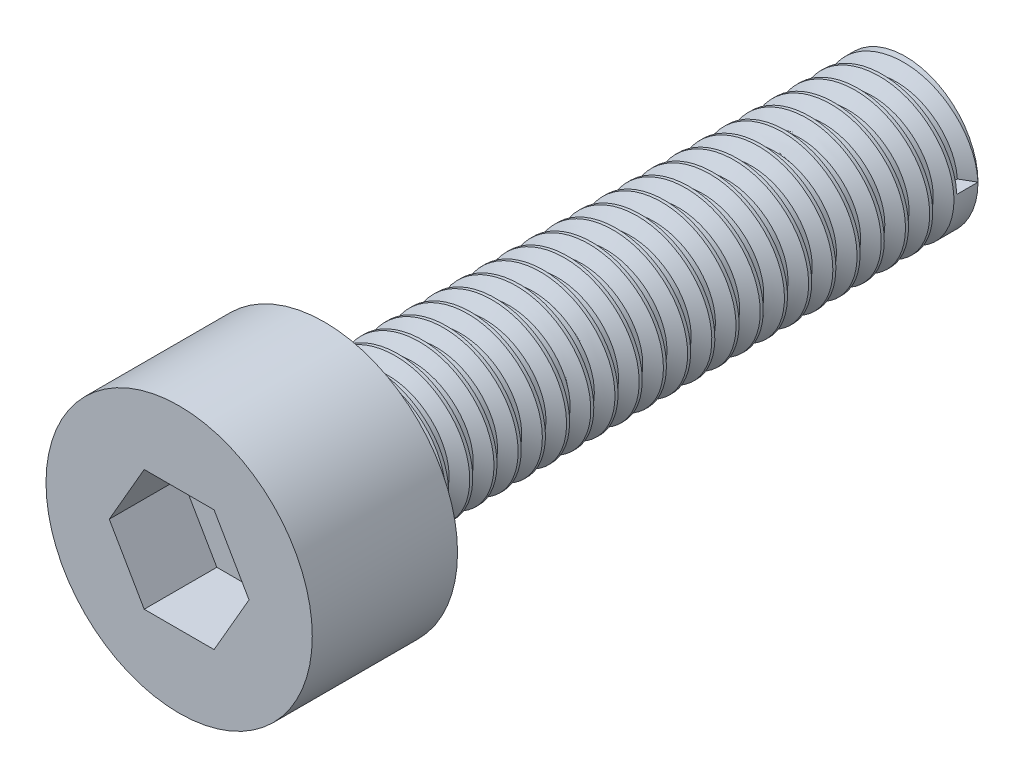
SolidWorks part; units mm, degrees
ref_plane "前视基准面" through (0, 0, 0) normal (0, 0, 1) x (1, 0, 0)
ref_plane "上视基准面" through (0, 0, 0) normal (0, 1, 0) x (1, 0, 0)
ref_plane "右视基准面" through (0, 0, 0) normal (1, 0, 0) x (0, 0, -1)
sketch "草图1" plane through (0, 0, 0) normal (0, 0, 1) x (1, 0, 0)
  circle A0 centre (0, 0) radius 1.5
  dimension "diameter" = 3
extrude "螺杆_直径3_长度10" add sketch "草图1" along normal blind 12
thread "真实螺纹_M3x0.5_右旋_长10" pitch 0.5 method cut profile "螺纹线轮廓1" start angle 0, offset 0, length 12, pitch 0.5, diameter 3
ref_plane "基准面4" through (1.5, 0, 0) normal (0, -1, 0) x (1, 0, 0)
sketch "螺纹线轮廓1" plane through (1.5, 0, 0) normal (0, -1, 0) x (1, 0, 0)
  line L0 (0, 0) -> (0, 0.5) construction
  line L11 (0, 0) -> (0, 0.4375)
  line L12 (0, 0.4375) -> (-0.2706, 0.2812)
  line L13 (-0.2706, 0.2812) -> (-0.2706, 0.1562)
  line L15 (-0.2706, 0.1562) -> (0, 0)
  line L17 (-0.2706, 0.2187) -> (0, 0.2187) construction
  point P2 (0, 0)
  dimension "Pitch" = 0.5
  dimension "Profile_Angle" = 60
  dimension "Profile_Land" = 0.125
  dimension "Profile_Height" = 0.2706
sketch "草图2" plane through (0, 0, 12) normal (0, 0, 1) x (1, 0, 0)
  circle A0 centre (0, 0) radius 2.75
  dimension "diameter" = 5.5
extrude "杯头_直径5.5_厚度3" add sketch "草图2" along normal blind 3
sketch "草图3" plane through (0, 0, 15) normal (0, 0, 1) x (1, 0, 0)
  line L0 (1.4434, 0) -> (0.7217, 1.25)
  line L1 (0.7217, 1.25) -> (-0.7217, 1.25)
  line L2 (-0.7217, 1.25) -> (-1.4434, 0)
  line L3 (-1.4434, 0) -> (-0.7217, -1.25)
  line L4 (-0.7217, -1.25) -> (0.7217, -1.25)
  line L5 (0.7217, -1.25) -> (1.4434, 0)
  dimension "x0" = 1.4434
  dimension "x1" = 0.7217
  dimension "x2" = 0.7217
  dimension "x3" = 1.4434
  dimension "x4" = 0.7217
  dimension "x5" = 0.7217
  dimension "y1" = 1.25
  dimension "y4" = 1.25
extrude "内六角_对边2.5_深1.5" cut sketch "草图3" against normal blind 1.5
